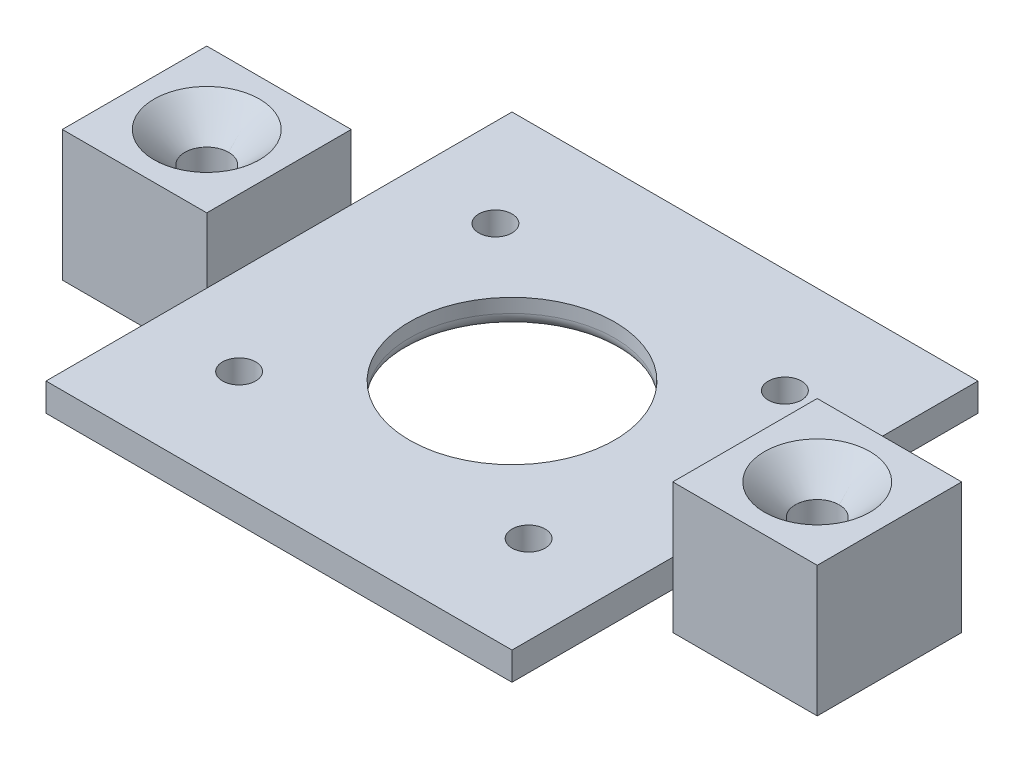
SolidWorks part; units mm, degrees
ref_plane "Front Plane" through (0, 0, 0) normal (0, 0, 1) x (1, 0, 0)
ref_plane "Top Plane" through (0, 0, 0) normal (0, 1, 0) x (1, 0, 0)
ref_plane "Right Plane" through (0, 0, 0) normal (1, 0, 0) x (0, 0, -1)
sketch "Sketch1" plane through (0, 0, 0) normal (0, 1, 0) x (1, 0, 0)
  line L1 (0, 0) -> (50, 0)
  line L2 (0, 0) -> (0, -50)
  line L3 (0, -50) -> (50, -50)
  line L4 (50, 0) -> (50, -50)
  dimension "D1" = 50
extrude "Boss-Extrude1" add sketch "Sketch1" along normal blind 3
sketch "Sketch2" plane through (0, 3, 0) normal (0, 1, 0) x (1, 0, 0)
  line L0 (0, 0) -> (50, -50) construction
  circle A0 centre (25, -25) radius 11
  dimension "D1" = 22
extrude "Cut-Extrude1" cut sketch "Sketch2" against normal through all both and the other way through all
sketch "Sketch3" plane through (0, 3, 0) normal (0, 1, 0) x (1, 0, 0)
  line L0 (11.25, -11.25) -> (38.75, -11.25) construction
  line L1 (50, 0) -> (0, 0) construction
  line L2 (0, -25) -> (60.337, -25) construction
  line L3 (0, 0) -> (0, -50) construction
  line L4 (11.25, -38.75) -> (38.75, -38.75) construction
  circle A0 centre (9.47, -11.25) radius 1.78
  circle A1 centre (40.53, -11.25) radius 1.78
  circle A4 centre (40.53, -38.75) radius 1.78
  circle A5 centre (9.47, -38.75) radius 1.78
  point P4 (25, 0)
  point P7 (25, -11.25)
  dimension "D3" = 3.56
extrude "Cut-Extrude2" cut sketch "Sketch3" against normal through all both and the other way through all
fillet "Fillet1" radius 1.5 1 edges at (25, 0, 36)
sketch "Sketch4" plane through (0, 0, 0) normal (0, -1, 0) x (1, 0, 0)
  line L0 (0, 25) -> (-26.2908, 25) construction
  line L1 (0, 0) -> (0, 50) construction
  line L2 (0, 32.75) -> (0, 17.25) construction
  line L3 (0, 32.75) -> (-15.5, 32.75)
  line L4 (-15.5, 32.75) -> (-15.5, 17.25)
  line L5 (-15.5, 17.25) -> (0, 17.25)
  line L6 (0, 17.25) -> (0, 32.75)
  line L7 (25, 50) -> (25, 58.4004) construction
  line L8 (0, 50) -> (50, 50) construction
  line L9 (65.5, 17.25) -> (50, 17.25)
  line L10 (65.5, 32.75) -> (65.5, 17.25)
  line L11 (50, 32.75) -> (65.5, 32.75)
  line L12 (50, 17.25) -> (50, 32.75)
  line L13 (-15.5, 32.75) -> (0, 17.25) construction
  circle A0 centre (-7.75, 25) radius 2.35
  circle A1 centre (57.75, 25) radius 2.35
  point P6 (0, 25)
  dimension "D3" = 4.7
  dimension "D4" = 4.7
  dimension "D1" = 15.5
  dimension "D2" = 15.5
extrude "Boss-Extrude3" add sketch "Sketch4" against normal blind 10
sketch "Sketch6" plane through (0, 0, 0) normal (0, -1, 0) x (1, 0, 0)
  line L1 (-15.5, 32.75) -> (0, 32.75)
  line L2 (-15.5, 32.75) -> (-15.5, 17.25)
  line L3 (-15.5, 17.25) -> (0, 17.25)
  line L4 (0, 32.75) -> (0, 17.25)
  line L5 (50, 32.75) -> (65.5, 32.75)
  line L6 (50, 32.75) -> (50, 17.25)
  line L7 (50, 17.25) -> (65.5, 17.25)
  line L8 (65.5, 32.75) -> (65.5, 17.25)
  circle A0 centre (-7.75, 25) radius 2.35
  circle A1 centre (57.75, 25) radius 2.35
extrude "Boss-Extrude4" add sketch "Sketch6" along normal blind 4
fillet "Fillet3" radius 3.3 2 edges at (-7.75, 10, 22.65) (57.75, 10, 22.65) conic radius 140
